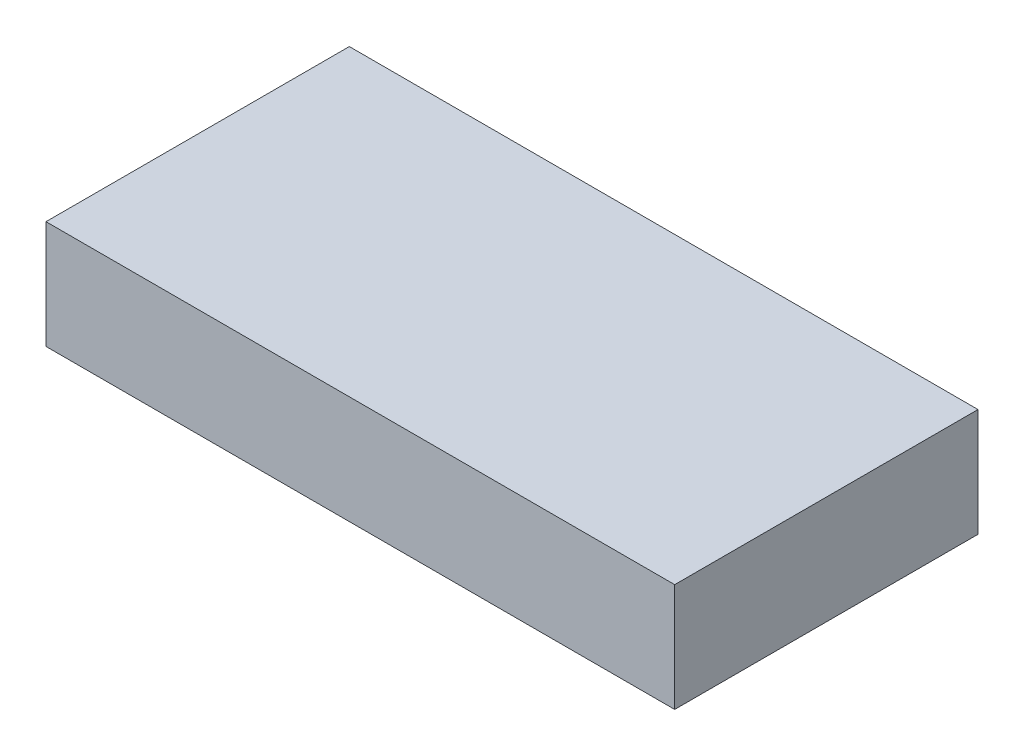
SolidWorks part; units mm, degrees
ref_plane "Front Plane" through (0, 0, 0) normal (0, 0, 1) x (1, 0, 0)
ref_plane "Top Plane" through (0, 0, 0) normal (0, 1, 0) x (1, 0, 0)
ref_plane "Right Plane" through (0, 0, 0) normal (1, 0, 0) x (0, 0, -1)
sketch "Sketch1" plane through (0, 0, 0) normal (0, 1, 0) x (1, 0, 0)
  line L1 (570, -275) -> (-570, -275)
  line L2 (570, -275) -> (570, 275)
  line L3 (570, 275) -> (-570, 275)
  line L4 (-570, -275) -> (-570, 275)
  line L5 (570, -275) -> (-570, 275) construction
  line L6 (570, 275) -> (-570, -275) construction
  point P0 (0, 0)
  dimension "D1" = 1140
  dimension "D2" = 550
extrude "Boss-Extrude1" add sketch "Sketch1" along normal blind 196
equation "\"assembly\" = 0"
equation "\"thickness 1\" = 3"
equation "\"thickness 2\" = 8"
equation "\"connecting flange\" = 50"
equation "\"main\" = 0"
equation "\"main length\" = 1200"
equation "\"main width\" = 1200"
equation "\"divider panel distance offset\" = 550"
equation "\"side panel\" = 0"
equation "\"access hatch length\" = 800"
equation "\"access hatch width\" = 350"
equation "\"access hatch offset X\" = 50"
equation "\"access hatch offset Y\" = 100"
equation "\"side panel length\" = 1200"
equation "\"side panel width\" = 1000"
equation "\"back panel\" = 0"
equation "\"back panel access hatch length\" = 1150"
equation "\"back panel access hatch width\" = 206"
equation "\"back panel access hatch flange\" = 40"
equation "\"drift eliminator\" = 0"
equation "\"drift eliminator size offset\" = 10"
equation "\"drift eliminator length\" = \"back panel access hatch length\" - \"drift eliminator size offset\""
equation "\"drift eliminator width\" = \"back panel access hatch width\" - \"drift eliminator size offset\""
equation "\"drift eliminator depth\" = \"divider panel distance offset\""
equation "\"sump\" = 0"
equation "\"D1@Boss-Extrude1\"=\"drift eliminator width\""
equation "\"D1@Sketch1\"=\"drift eliminator length\""
equation "\"D2@Sketch1\"=\"drift eliminator depth\""
